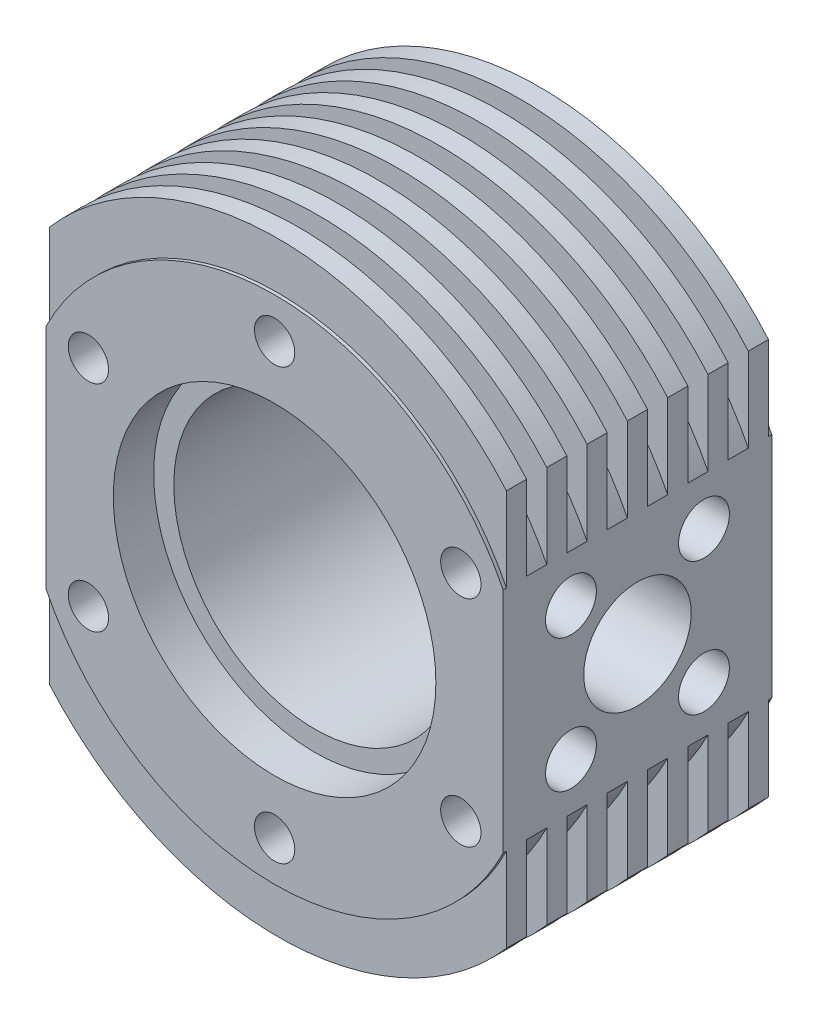
SolidWorks part; units mm, degrees
ref_plane "Front Plane" through (0, 0, 0) normal (0, 0, 1) x (1, 0, 0)
ref_plane "Top Plane" through (0, 0, 0) normal (0, 1, 0) x (1, 0, 0)
ref_plane "Right Plane" through (0, 0, 0) normal (1, 0, 0) x (0, 0, -1)
sketch "Sketch1" plane through (0, 0, 0) normal (0, 0, 1) x (1, 0, 0)
  line L2 (17, -14.7394) -> (17, 14.7394)
  line L4 (-17, -14.7394) -> (-17, 14.7394)
  line L5 (13.2662, -18.173) -> (-13.2662, 18.173) construction
  line L6 (13.2662, 18.173) -> (-13.2662, -18.173) construction
  arc A0 (-17, -14.7394) -> (17, -14.7394) centre (0, 0) ccw
  arc A1 (17, 14.7394) -> (-17, 14.7394) centre (0, 0) ccw
  circle A2 centre (0, 0) radius 10.5
  dimension "D1" = 45
  dimension "D2" = 21
extrude "Boss-Extrude1" add sketch "Sketch1" along normal blind 20
sketch "Sketch2" plane through (0, 0, 20) normal (0, 0, 1) x (1, 0, 0)
  circle A0 centre (0, 0) radius 12
  dimension "D1" = 24
extrude "Cut-Extrude1" cut sketch "Sketch2" against normal blind 3
sketch "Sketch4" plane through (0, 0, 0) normal (0, 0, -1) x (-1, 0, 0)
  circle A0 centre (0, 0) radius 19
  dimension "D1" = 38
extrude "Cut-Extrude2" cut sketch "Sketch4" against normal blind 0.25 flip side to cut
sketch "Sketch5" plane through (0, 0, 20) normal (0, 0, 1) x (1, 0, 0)
  circle A0 centre (0, 0) radius 19
  dimension "D1" = 38
extrude "Cut-Extrude3" cut sketch "Sketch5" against normal blind 0.25 flip side to cut
ref_plane "Plane1" through (0, 0, 18.25) normal (0, 0, 1) x (1, 0, 0)
sketch "Sketch6" plane through (0, 0, 18.25) normal (0, 0, 1) x (1, 0, 0)
  line L0 (17, 8.4853) -> (17, 14.7394) construction
  line L1 (17, 8.4853) -> (17, 14.7394)
  line L2 (-17, 14.7394) -> (-17, 8.4853) construction
  line L3 (-17, 14.7394) -> (-17, 8.4853)
  arc A0 (17, 8.4853) -> (-17, 8.4853) centre (0, 0) ccw construction
  arc A1 (17, 14.7394) -> (-17, 14.7394) centre (0, 0) ccw construction
  arc A2 (17, 8.4853) -> (-17, 8.4853) centre (0, 0) ccw
  arc A3 (17, 14.7394) -> (-17, 14.7394) centre (0, 0) ccw
extrude "Cut-Extrude4" cut sketch "Sketch6" against normal blind 1.5
pattern_linear "LPattern1" count 6 spacing 3 along (0, 0, -1) of "Cut-Extrude4"
mirror "Mirror1" about plane through (0, 0, 0) normal (0, 1, 0) of "LPattern1"
sketch "Sketch9" plane through (17, 0, 0) normal (1, 0, 0) x (0, 0, -1)
  circle A0 centre (-10, 0) radius 4
  dimension "D2" = 8
  dimension "D1" = 10
extrude "Cut-Extrude5" cut sketch "Sketch9" against normal up to next
sketch "Sketch10" plane through (17, 0, 0) normal (1, 0, 0) x (0, 0, -1)
  line L0 (-10, 0) -> (-3, 0) construction
  line L1 (-10, 0) -> (-5.0503, 4.9497) construction
  line L2 (-10, 0) -> (-10, -7) construction
  circle A0 centre (-10, 0) radius 7 construction
  circle A1 centre (-5.0503, 4.9497) radius 1.8925
  circle A2 centre (-5.0503, -4.9497) radius 1.8925
  circle A3 centre (-14.9497, -4.9497) radius 1.8925
  circle A4 centre (-14.9497, 4.9497) radius 1.8925
  dimension "D1" = 14
  dimension "D3" = 3.785
  dimension "D2" = 45
extrude "Cut-Extrude6" cut sketch "Sketch10" against normal blind 4
ref_plane "Plane2" through (0, 0, 10) normal (0, 0, 1) x (1, 0, 0)
sketch "Sketch11" plane through (0, 0, 10) normal (0, 0, 1) x (1, 0, 0)
  line L0 (-17, 0) -> (-11.5, 0)
  line L1 (-17, 8.4853) -> (-17, -8.4853) construction
  line L2 (-11.5, 0) -> (-14.5, -3)
  line L3 (-14.5, -3) -> (-17, -3)
  line L4 (-17, 0) -> (-17, -3)
  dimension "D1" = 2.5
  dimension "D2" = 3
  dimension "D3" = 45
revolve "Cut-Revolve1" cut sketch "Sketch11" angle 360 about L0
mirror "Mirror2" about plane through (0, 0, 0) normal (1, 0, 0) of "Cut-Extrude6"
sketch "Sketch12" plane through (0, 0, 20) normal (0, 0, 1) x (1, 0, 0)
  circle A0 centre (0, 0) radius 16 construction
  circle A1 centre (0, 16) radius 1.5
  circle A2 centre (13.8564, 8) radius 1.5
  circle A3 centre (13.8564, -8) radius 1.5
  circle A4 centre (0, -16) radius 1.5
  circle A5 centre (-13.8564, -8) radius 1.5
  circle A6 centre (-13.8564, 8) radius 1.5
  point P17 (0, 0)
  dimension "D1" = 32
  dimension "D2" = 3
  dimension "D3" = 6
extrude "Cut-Extrude7" cut sketch "Sketch12" against normal blind 4
mirror "Mirror3" about plane through (0, 0, 10) normal (0, 0, 1) of "Cut-Extrude7"
